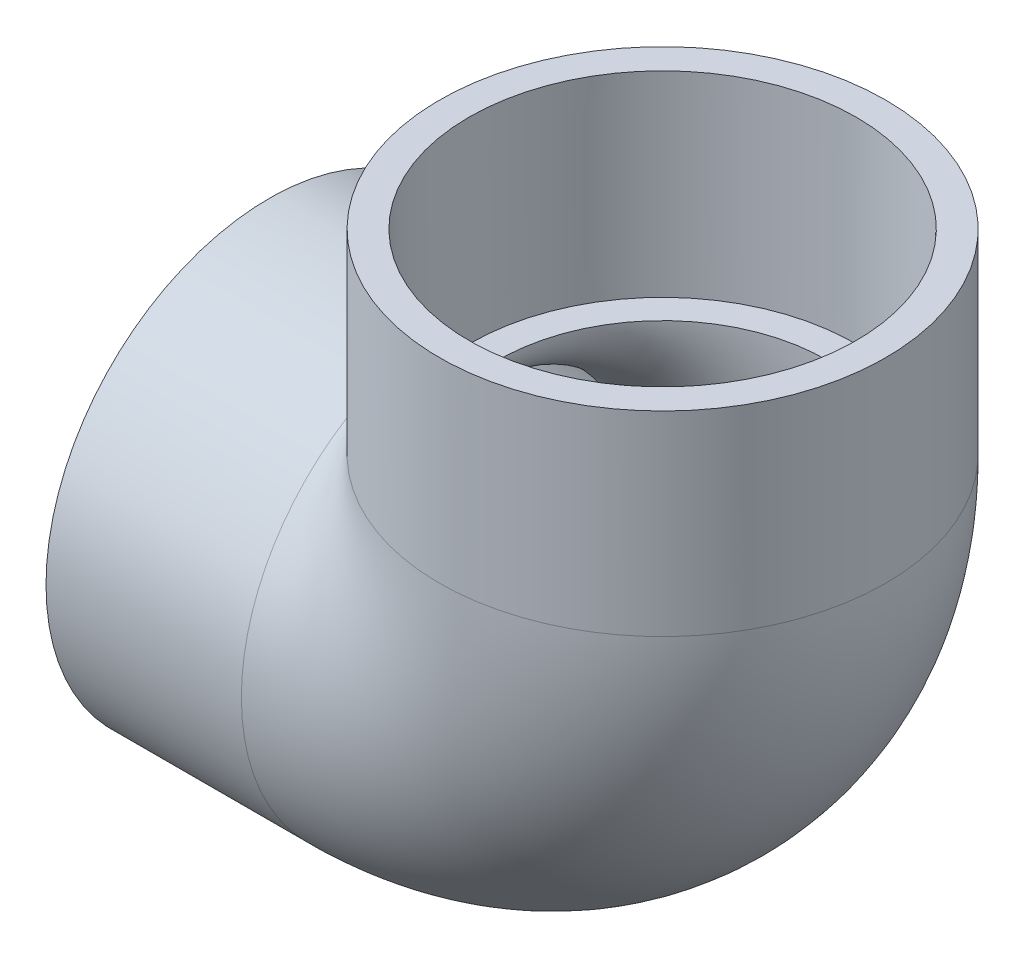
SolidWorks part; units mm, degrees
ref_plane "Front Plane" through (0, 0, 0) normal (0, 0, 1) x (1, 0, 0)
ref_plane "Top Plane" through (0, 0, 0) normal (0, 1, 0) x (1, 0, 0)
ref_plane "Right Plane" through (0, 0, 0) normal (1, 0, 0) x (0, 0, -1)
sketch "sKETCH" plane through (0, 0, 0) normal (0, 0, 1) x (1, 0, 0)
  line L0 (-116.6368, 0) -> (0, 0) construction
  line L1 (0, 0) -> (0, 116.6368) construction
  line L2 (-58.7248, 0) -> (0, 0) construction
  line L3 (0, 0) -> (0, 58.7248) construction
  line L4 (-116.6368, 66.1416) -> (-116.6368, -66.1416) construction
  line L5 (-58.7248, 57.0357) -> (-116.6368, 57.3786) construction
  line L6 (-58.7248, 57.0357) -> (-58.7248, -57.0357) construction
  line L7 (-58.7248, -57.0357) -> (-116.6368, -57.3786) construction
  line L8 (-116.6368, 57.3786) -> (-116.6368, -57.3786) construction
  line L9 (-66.1416, 116.6368) -> (66.1416, 116.6368) construction
  line L10 (-57.3786, 116.6368) -> (57.3786, 116.6368) construction
  line L11 (57.3786, 116.6368) -> (57.0357, 58.7248) construction
  line L12 (57.0357, 58.7248) -> (-57.0357, 58.7248) construction
  line L13 (-57.0357, 58.7248) -> (-57.3786, 116.6368) construction
  line L14 (-58.7248, 48.5902) -> (-58.7248, -48.5902) construction
  line L18 (-48.5902, 58.7248) -> (48.5902, 58.7248) construction
  dimension "H" = 116.6368
  dimension "BendRadius" = 58.7248
  dimension "M" = 132.2832
  dimension "OD A" = 114.7572
  dimension "OD B" = 114.0714
  dimension "ID" = 97.1804
  dimension "BendAngle" = 90
sketch "ElbowArc" plane through (0, 0, 0) normal (0, 0, 1) x (1, 0, 0)
  line L0 (57.0357, 58.7248) -> (-57.0357, 58.7248) construction
  line L1 (-58.7248, 58.7248) -> (0, 58.7248) construction
  line L2 (-58.7248, 58.7248) -> (-58.7248, 0) construction
  arc A0 (0, 58.7248) -> (-58.7248, 0) centre (-58.7248, 58.7248) cw construction
  point P7 (0, 58.7248)
  point P8 (-58.7248, 0)
  dimension "BendRadius" = 58.7248
  dimension "BendAngle" = 90
sketch "Sketch1" plane through (0, 0, 0) normal (0, 0, 1) x (1, 0, 0)
  line L0 (-116.6368, 0) -> (0, 0) construction
  line L1 (-116.6368, 0) -> (0, 0) construction
  line L3 (-116.6368, -66.1416) -> (-58.7248, -66.1416)
  line L4 (-116.6368, -66.1416) -> (-116.6368, -57.3786)
  line L5 (-116.6368, -57.3786) -> (-58.7248, -57.0357)
  line L6 (-58.7248, -66.1416) -> (-58.7248, -57.0357)
revolve "Revolve1" add sketch "Sketch1" angle 360 about L1
sketch "Sketch2" plane through (0, 0, 0) normal (0, 0, 1) x (1, 0, 0)
  line L0 (57.3786, 116.6368) -> (57.0357, 58.7248)
  line L1 (57.0357, 58.7248) -> (66.1416, 58.7248)
  line L2 (66.1416, 58.7248) -> (66.1416, 116.6368)
  line L3 (66.1416, 116.6368) -> (57.3786, 116.6368)
  line L4 (0, 0) -> (0, 116.6368) construction
  line L5 (0, 0) -> (0, 116.6368) construction
revolve "Revolve2" add sketch "Sketch2" angle 360 about L5
sketch "Sketch3" plane through (-58.7248, 0, 0) normal (1, 0, 0) x (0, 0, -1)
  circle A0 centre (0, 0) radius 48.5902
  circle A1 centre (0, 0) radius 66.1416
sketch "Sketch4" plane through (0, 0, 0) normal (0, 0, 1) x (1, 0, 0)
  line L0 (-116.6368, 0) -> (0, 0) construction
  line L1 (0, 0) -> (0, 116.6368) construction
  line L2 (-116.6368, 0) -> (-58.7248, 0) construction
  line L3 (0, 58.7248) -> (0, 116.6368) construction
  arc A0 (-58.7248, 0) -> (0, 58.7248) centre (-58.7248, 58.7248) ccw
sweep "Sweep1" add profiles "Sketch3" path "Sketch4"
other "CPoint1" parameters "Diameter"=101.6, "StubLength"=152.4
ref_axis "Axis1" through (0, 68.7248, 0) along (0, -1, 0)
other "CPoint2" parameters "Diameter"=101.6, "StubLength"=152.4
ref_axis "Axis2" through (-68.7248, 0, 0) along (1, 0, 0)
other "RPoint1"
